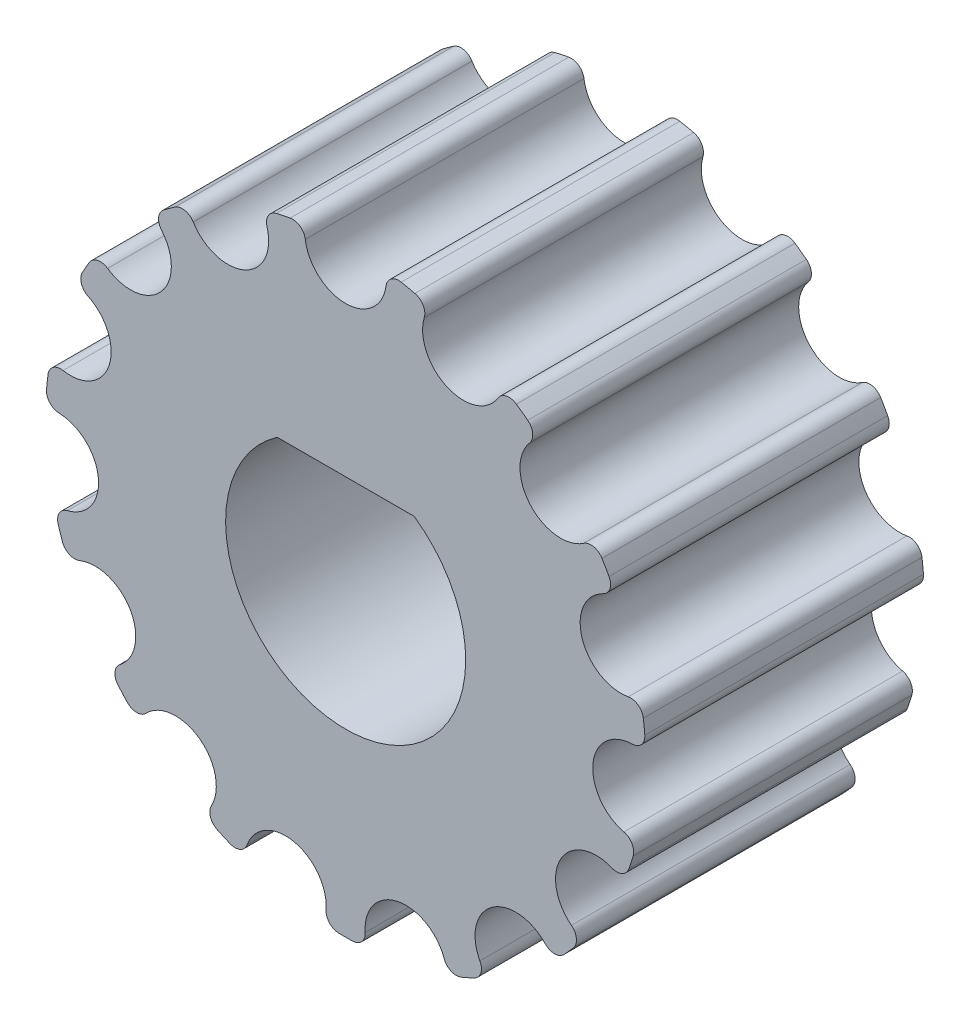
SolidWorks part; units mm, degrees
ref_plane "Ebene vorne" through (0, 0, 0) normal (0, 0, 1) x (1, 0, 0)
ref_plane "Ebene oben" through (0, 0, 0) normal (0, 1, 0) x (1, 0, 0)
ref_plane "Ebene rechts" through (0, 0, 0) normal (1, 0, 0) x (0, 0, -1)
sketch "Skizze1" plane through (0, 0, 0) normal (0, 0, 1) x (1, 0, 0)
  circle A0 centre (0, 0) radius 7
  dimension "D1" = 14
extrude "Aufsatz-Linear austragen1" add sketch "Skizze1" along normal mid plane 6.5
sketch "Skizze2" plane through (0, 0, 0) normal (0, 0, 1) x (1, 0, 0)
  line L0 (0, 0) -> (0, 7) construction
  line L1 (0.95, 6.75) -> (0.95, 7)
  line L2 (0.95, 7) -> (-0.95, 7)
  line L3 (-0.95, 7) -> (-0.95, 6.75)
  circle A0 centre (0, 0) radius 7 construction
  arc A1 (-0.95, 6.75) -> (0.95, 6.75) centre (0, 6.75) ccw
  point P12 (0, 7)
  dimension "D1" = 1.9
  dimension "D2" = 1.2
extrude "Schnitt-Linear austragen1" cut sketch "Skizze2" against normal through all both and the other way through all
fillet "Verrundung2" radius 0.3 2 edges at (0.95, 6.9352, 0) (-0.95, 6.9352, 0)
pattern_circular "Kreismuster1" count 15 over 360 about axis through (0, 0, 3.25) along (0, 0, -1) of "Schnitt-Linear austragen1", "Verrundung2"
ref_axis "Achse1" through (0, 0, -3.575) along (0, 0, 1)
sketch "Skizze3" plane through (0, 0, 0) normal (0, 0, 1) x (1, 0, 0)
  line L0 (1.5, 2) -> (-1.5, 2) construction
  line L1 (1.5969, 2.3) -> (-1.5969, 2.3)
  arc A0 (-1.5, 2) -> (1.5, 2) centre (0, 0) ccw construction
  arc A1 (-1.5969, 2.3) -> (1.5969, 2.3) centre (0, 0) ccw
  dimension "D1" = 5
  dimension "D2" = 4.5
  dimension "D3" = 0.3
extrude "Schnitt-Linear austragen2" cut sketch "Skizze3" against normal through all both and the other way through all
